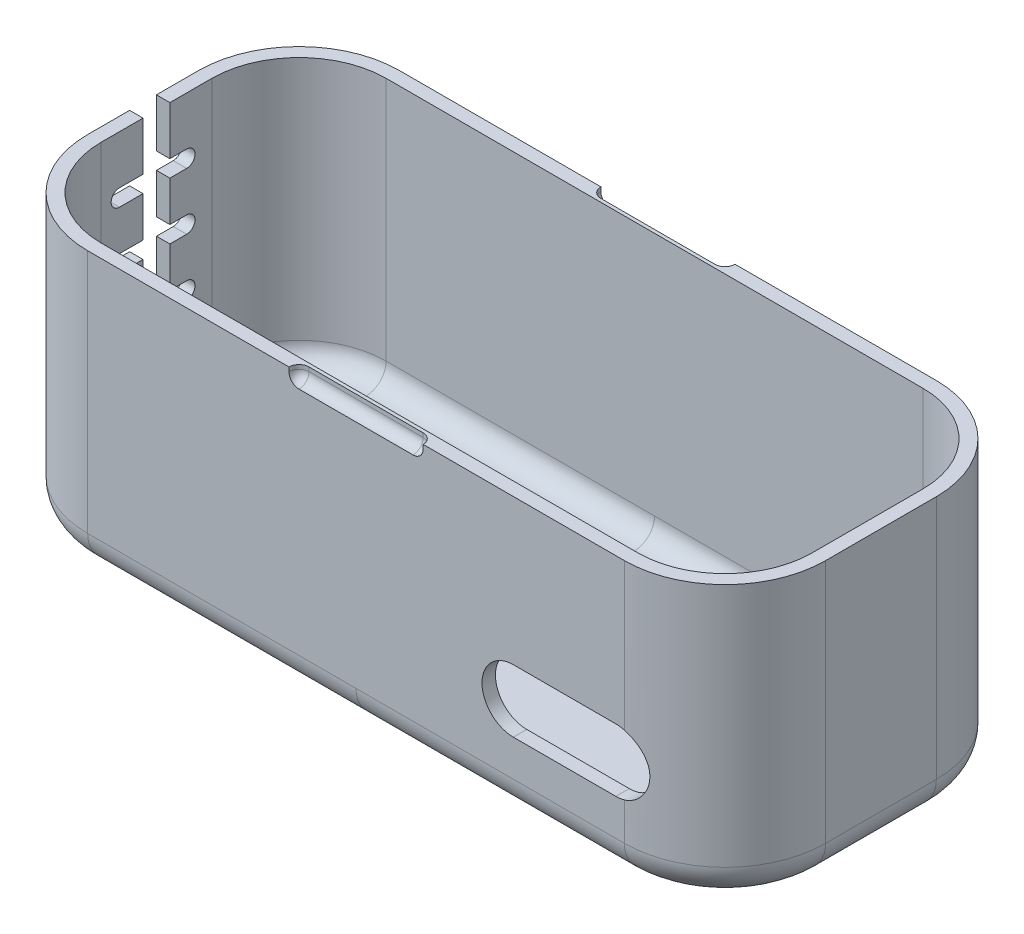
SolidWorks part; units mm, degrees
ref_plane "前基準面" through (0, 0, 0) normal (0, 0, 1) x (1, 0, 0)
ref_plane "上基準面" through (0, 0, 0) normal (0, 1, 0) x (1, 0, 0)
ref_plane "右基準面" through (0, 0, 0) normal (1, 0, 0) x (0, 0, -1)
sketch "草圖1" plane through (0, 0, 0) normal (0, 1, 0) x (1, 0, 0)
  line L0 (0, -55) -> (0, 55) construction
  line L1 (0, 46.5) -> (-110, 46.5)
  line L2 (0, 46.5) -> (0, -46.5)
  line L3 (0, -46.5) -> (-110, -46.5)
  line L4 (-110, 46.5) -> (-110, -46.5)
  dimension "D1" = 93
  dimension "D3" = 110
extrude "填料-伸長1" add sketch "草圖1" along normal blind 83
fillet "圓角8" radius 30 2 edges at (-110, 41.5, -46.5) (-110, 41.5, 46.5)
fillet "圓角9" radius 10 5 edges at (-40, 0, -46.5) (-101.2132, 0, -37.7132) (-110, 0, 0) (-101.2132, 0, 37.7132) (-40, 0, 46.5)
mirror "鏡射1" about plane through (0, 0, 0) normal (1, 0, 0) of "圓角8", "圓角9", "填料-伸長1"
shell "薄殼1" thickness 4 removed face at (0, 83, 0)
sketch "草圖2" plane through (0, 0, 46.5) normal (0, 0, 1) x (1, 0, 0)
  line L0 (-80, 83) -> (80, 83) construction
  line L1 (-20, 83) -> (20, 83)
  line L2 (-20, 83) -> (-20, 78.5255)
  line L3 (-20, 78.5255) -> (20, 78.5255)
  line L4 (20, 83) -> (20, 78.5255)
  line L5 (0, -55) -> (0, 55) construction
  dimension "D1" = 40
  dimension "D2" = 20
extrude "填料-伸長2" add sketch "草圖2" against normal blind 3
sketch "草圖3" plane through (0, 0, 46.5) normal (0, 0, 1) x (1, 0, 0)
  line L0 (-80, 83) -> (80, 83) construction
  line L1 (-20, 83) -> (20, 83)
  line L2 (-20, 83) -> (-20, 78.7757)
  line L3 (-20, 78.7757) -> (20, 78.7757)
  line L4 (20, 83) -> (20, 78.7757)
  line L5 (0, -55) -> (0, 55) construction
  dimension "D1" = 40
  dimension "D2" = 20
extrude "除料-伸長1" cut sketch "草圖3" against normal blind 3
fillet "圓角11" radius 3 3 edges at (0, 78.7757, 43.5) (-20, 80.8878, 43.5) (20, 80.8878, 43.5)
mirror "鏡射2" about plane through (0, 0, 0) normal (0, 0, 1) of "圓角11", "除料-伸長1"
sketch "草圖4" plane through (-110, 0, 0) normal (-1, 0, 0) x (0, 0, 1)
  line L0 (-16.5, 83) -> (16.5, 83) construction
  line L1 (-4, 83) -> (4, 83)
  line L2 (-4, 83) -> (-4, 15)
  line L3 (-4, 15) -> (4, 15)
  line L4 (4, 83) -> (4, 15)
  line L5 (0, -55) -> (0, 55) construction
  line L6 (-9, 32) -> (11, 32) construction
  line L9 (-9, 34.5) -> (11, 34.5)
  line L12 (-9, 29.5) -> (11, 29.5)
  line L15 (-9, 49) -> (11, 49) construction
  line L20 (-9, 15) -> (11, 15) construction
  line L21 (-9, 17.5) -> (11, 17.5)
  line L22 (-9, 12.5) -> (11, 12.5)
  line L23 (-9, 51.5) -> (11, 51.5)
  line L27 (-9, 46.5) -> (11, 46.5)
  line L28 (-9, 66) -> (11, 66) construction
  line L29 (-9, 68.5) -> (11, 68.5)
  line L30 (-9, 63.5) -> (11, 63.5)
  arc A10 (-9, 17.5) -> (-9, 12.5) centre (-9, 15) ccw
  arc A11 (11, 12.5) -> (11, 17.5) centre (11, 15) ccw
  arc A14 (-9, 34.5) -> (-9, 29.5) centre (-9, 32) ccw
  arc A15 (11, 29.5) -> (11, 34.5) centre (11, 32) ccw
  arc A16 (-9, 51.5) -> (-9, 46.5) centre (-9, 49) ccw
  arc A17 (11, 46.5) -> (11, 51.5) centre (11, 49) ccw
  arc A18 (-9, 68.5) -> (-9, 63.5) centre (-9, 66) ccw
  arc A19 (11, 63.5) -> (11, 68.5) centre (11, 66) ccw
  point P11 (1, 32)
  point P20 (1, 49)
  point P27 (1, 66)
  point P40 (1, 15)
  point P52 (0, 32.1)
  line M16 (16.5, 83) -> (-16.5, 83)
  dimension "D1" = 8
  dimension "D2" = 4
  dimension "D3" = 4
  dimension "D7" = 68
extrude "除料-伸長2" cut sketch "草圖4" against normal up to next contours L2 L29 L4 M16 | L30 L2 L23 L4 | L2 L30 L4 L29 | L29 A18 L30 L2 | L2 L27 L4 L23 | L27 A17 L23 L4 | L27 L2 L9 L4 | L2 L12 L4 L9 | L9 A14 L12 L2 | L12 A15 L9 L4 | L2 L21 L4 L12 | L22 A11 L21 L4 L3 L2 A10 | L30 A19 L29 A18 | L27 A17 L23 A16 | L21 A11 L22 A10 region at (-110, 75.75, 0) region at (-110, 66, 0) region at (-110, 66, -7.5041) region at (-110, 57.5, 0) region at (-110, 49, 0) region at (-110, 49, 8.4991) region at (-110, 40.5, 0) region at (-110, 32, 0) region at (-110, 32, -7.5041) region at (-110, 32, 8.4991) region at (-110, 23.5, 0) region at (-110, 14.7491, 1.2007)
sketch "草圖5" plane through (0, 0, 46.5) normal (0, 0, 1) x (1, 0, 0)
  line L0 (46.9198, 30.2172) -> (77.4658, 30.2172) construction
  line L1 (46.9198, 39.5737) -> (77.4658, 39.5737)
  line L2 (46.9198, 20.8608) -> (77.4658, 20.8608)
  arc A0 (46.9198, 39.5737) -> (46.9198, 20.8608) centre (46.9198, 30.2172) ccw
  arc A1 (77.4658, 20.8608) -> (77.4658, 39.5737) centre (77.4658, 30.2172) ccw
  point P2 (62.1928, 30.2172)
extrude "除料-伸長3" cut sketch "草圖5" against normal up to next
